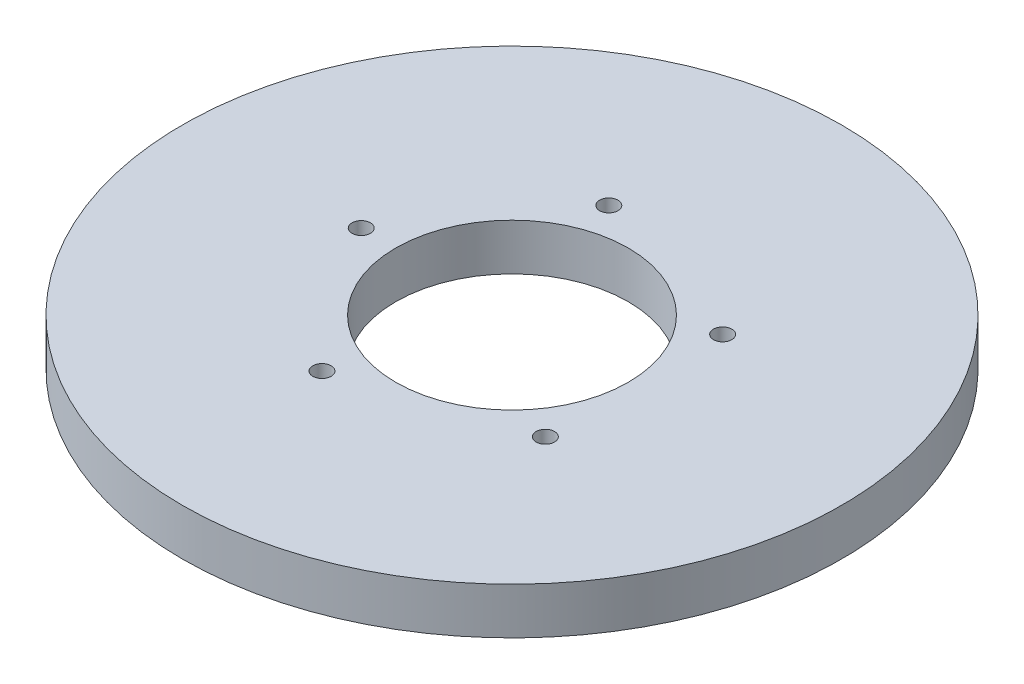
SolidWorks part; units mm, degrees
ref_plane "Front Plane" through (0, 0, 0) normal (0, 0, 1) x (1, 0, 0)
ref_plane "Top Plane" through (0, 0, 0) normal (0, 1, 0) x (1, 0, 0)
ref_plane "Right Plane" through (0, 0, 0) normal (1, 0, 0) x (0, 0, -1)
sketch "Sketch1" plane through (0, 0, 0) normal (0, 1, 0) x (1, 0, 0)
  circle A0 centre (0, 0) radius 85
  dimension "FLANGE_OD" = 170
extrude "Boss-Extrude1" add sketch "Sketch1" along normal blind 12
sketch "Sketch2" plane through (0, 0, 0) normal (0, 1, 0) x (1, 0, 0)
  circle A0 centre (0, 0) radius 30
  dimension "BORE_D" = 60
extrude "Cut-Extrude1" cut sketch "Sketch2" along normal through all
sketch "Sketch3" plane through (0, 12, 0) normal (0, 1, 0) x (1, 0, 0)
  circle A0 centre (0, 0) radius 38.8956 construction
  circle A1 centre (-38.8956, 0) radius 2.3661
  dimension "BOLT_D" = 4.7323
  dimension "BOLT_PCD" = 77.7912
extrude "Cut-Extrude2" cut sketch "Sketch3" against normal blind 10.7823
pattern_circular "CirPattern1" count 5 over 360 about axis through (0, 0, 0) along (0, 1, 0) of "Cut-Extrude2"
